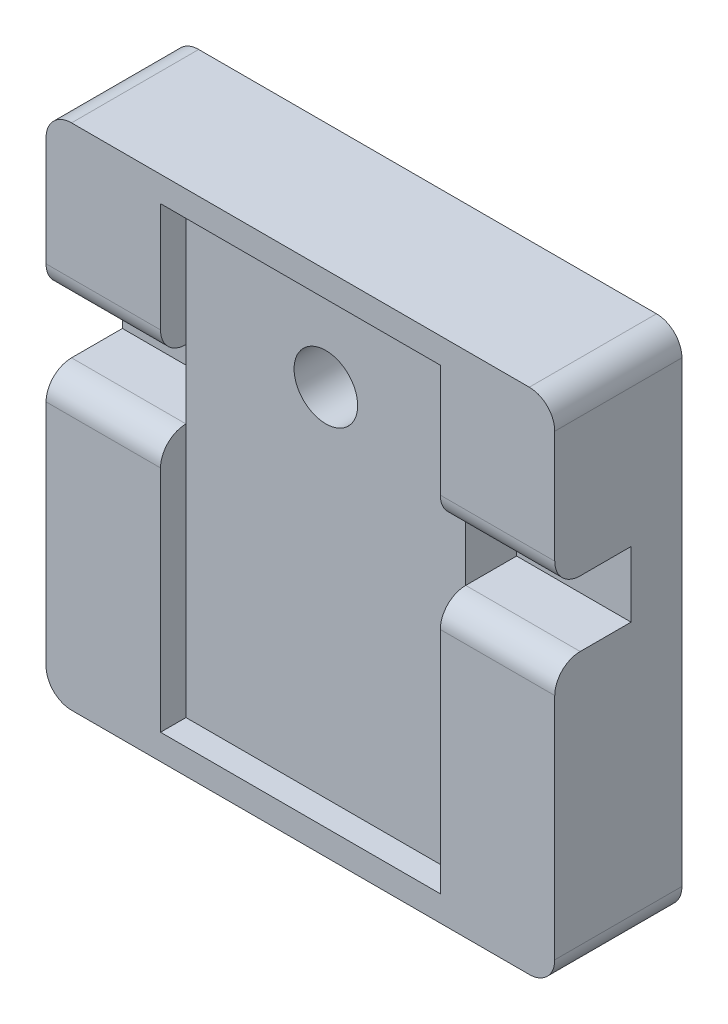
SolidWorks part; units mm, degrees
ref_plane "Спереди" through (0, 0, 0) normal (0, 0, 1) x (1, 0, 0)
ref_plane "Сверху" through (0, 0, 0) normal (0, 1, 0) x (1, 0, 0)
ref_plane "Справа" through (0, 0, 0) normal (1, 0, 0) x (0, 0, -1)
sketch "Эскиз1" plane through (0, 0, 0) normal (0, 0, 1) x (1, 0, 0)
  line L1 (-10, 10) -> (10, 10)
  line L2 (-10, 10) -> (-10, -10)
  line L3 (-10, -10) -> (10, -10)
  line L4 (10, 10) -> (10, -10)
  line L5 (-10, 10) -> (10, -10) construction
  line L6 (-10, -10) -> (10, 10) construction
  point P0 (0, 0)
  dimension "D1" = 20
  dimension "D2" = 20
extrude "Бобышка-Вытянуть1" add sketch "Эскиз1" along normal blind 5
sketch "Эскиз2" plane through (0, 0, 5) normal (0, 0, 1) x (1, 0, 0)
  line L0 (0, 10) -> (0, -10) construction
  line L1 (10, 10) -> (-10, 10) construction
  line L2 (-10, -10) -> (10, -10) construction
  line L3 (-10, 0) -> (10, 0) construction
  line L4 (-10, 10) -> (-10, -10) construction
  line L5 (10, -10) -> (10, 10) construction
  line L6 (-5.5, 5) -> (5.5, 5) construction
  line L7 (-5.5, 9) -> (5.5, 9)
  line L8 (-5.5, 9) -> (-5.5, -9)
  line L9 (-5.5, -9) -> (5.5, -9)
  line L10 (5.5, 9) -> (5.5, -9)
  line L11 (-5.5, 9) -> (5.5, -9) construction
  line L12 (-5.5, -9) -> (5.5, 9) construction
  circle A0 centre (0, 5) radius 1.25
  point P12 (0, 0)
  dimension "D4" = 2.5
  dimension "D1" = 11
  dimension "D2" = 18
  dimension "D3" = 4
extrude "Вырез-Вытянуть1" cut sketch "Эскиз2" against normal blind 1
extrude "Вырез-Вытянуть2" cut sketch "Эскиз2<2>" against normal through all contours A0 region at (0, 5, 5)
sketch "Эскиз2<2>" plane through (0, 0, 5) normal (0, 0, 1) x (1, 0, 0) same geometry as "Эскиз2"
sketch "Эскиз3" plane through (0, 0, 5) normal (0, 0, 1) x (1, 0, 0)
  line L0 (-10, 10) -> (-10, -10) construction
  line L1 (-10, 3.7) -> (-5.5, 3.7)
  line L2 (-10, 3.7) -> (-10, 1)
  line L3 (-10, 1) -> (-5.5, 1)
  line L4 (-5.5, 3.7) -> (-5.5, 1)
  line L5 (-5.5, 9) -> (-5.5, -9) construction
  line L6 (10, 10) -> (-10, 10) construction
  line L7 (5.5, -9) -> (5.5, 9) construction
  line L8 (5.5, 1) -> (10, 1)
  line L9 (5.5, 1) -> (5.5, 3.5749)
  line L10 (5.5, 3.5749) -> (10, 3.5749)
  line L11 (10, 1) -> (10, 3.5749)
  line L12 (10, -10) -> (10, 10) construction
  dimension "D1" = 2.7
  dimension "D2" = 6.3
extrude "Вырез-Вытянуть3" cut sketch "Эскиз3" against normal blind 3
fillet "Скругление1" radius 1 8 edges at (7.75, 1, 5) (7.75, 3.5749, 5) (-7.75, 1, 5) (-7.75, 3.7, 5) (-10, -10, 2.5) (10, -10, 2.5) (10, 10, 2.5) (-10, 10, 2.5)
